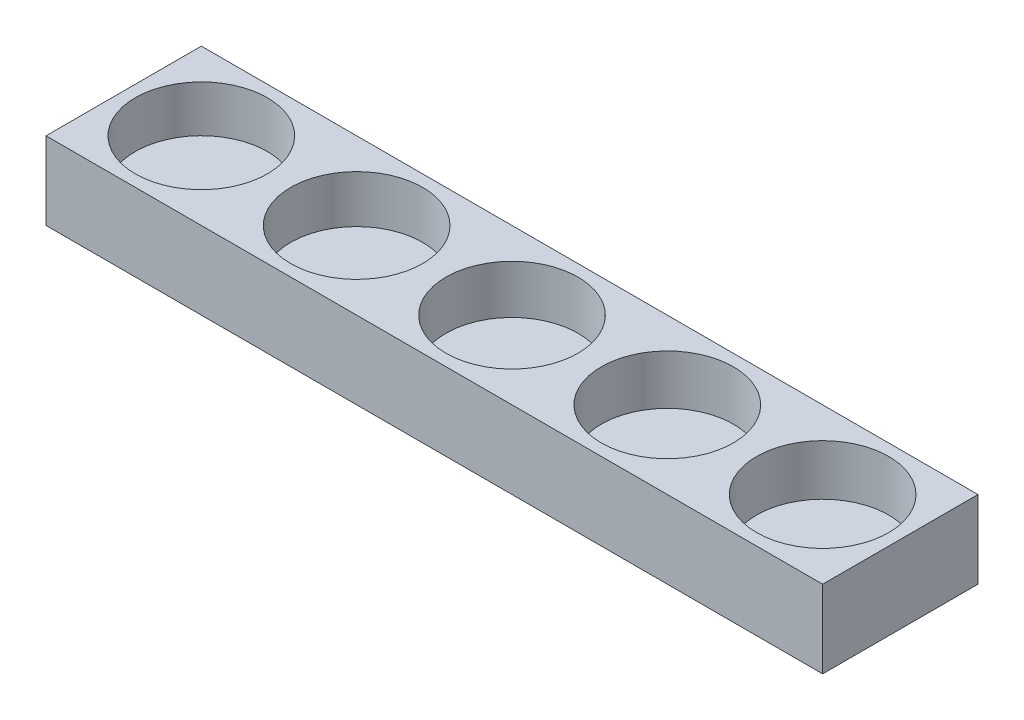
SolidWorks part; units mm, degrees
ref_plane "Front Plane" through (0, 0, 0) normal (0, 0, 1) x (1, 0, 0)
ref_plane "Top Plane" through (0, 0, 0) normal (0, 1, 0) x (1, 0, 0)
ref_plane "Right Plane" through (0, 0, 0) normal (1, 0, 0) x (0, 0, -1)
sketch "Sketch1" plane through (0, 0, 0) normal (0, 1, 0) x (1, 0, 0)
  line L0 (-75, 0) -> (75, 0) construction
  line L1 (75, -15) -> (-75, -15)
  line L2 (75, -15) -> (75, 15)
  line L3 (75, 15) -> (-75, 15)
  line L4 (-75, -15) -> (-75, 15)
  line L5 (75, -15) -> (-75, 15) construction
  line L6 (75, 15) -> (-75, -15) construction
  circle A0 centre (-60, 0) radius 5
  circle A1 centre (-30, 0) radius 5
  circle A2 centre (0, 0) radius 5
  circle A3 centre (30, 0) radius 5
  circle A4 centre (60, 0) radius 5
  point P0 (0, 0)
  dimension "D3" = 10
  dimension "D1" = 150
  dimension "D2" = 30
  dimension "D4" = 15
  dimension "D6" = 30
  dimension "D5" = 5
extrude "Boss-Extrude1" add sketch "Sketch1" along normal blind 5
sketch "Sketch2" plane through (0, 5, 0) normal (0, 1, 0) x (1, 0, 0)
  line L1 (-75, 15) -> (75, 15)
  line L2 (-75, 15) -> (-75, -15)
  line L3 (-75, -15) -> (75, -15)
  line L4 (75, 15) -> (75, -15)
extrude "Boss-Extrude2" add sketch "Sketch2" along normal blind 10
sketch "Sketch3" plane through (0, 15, 0) normal (0, 1, 0) x (1, 0, 0)
  circle A0 centre (60, 0) radius 5 construction
  circle A1 centre (30, 0) radius 5 construction
  circle A2 centre (0, 0) radius 5 construction
  circle A3 centre (-30, 0) radius 5 construction
  circle A4 centre (-60, 0) radius 5 construction
  circle A5 centre (60, 0) radius 5 construction
  circle A6 centre (30, 0) radius 5 construction
  circle A7 centre (0, 0) radius 5 construction
  circle A8 centre (-30, 0) radius 5 construction
  circle A9 centre (-60, 0) radius 5 construction
  circle A10 centre (-60, 0) radius 12.75
  circle A11 centre (-30, 0) radius 12.75
  circle A12 centre (0, 0) radius 12.75
  circle A13 centre (30, 0) radius 12.75
  circle A14 centre (60, 0) radius 12.75
  dimension "D1" = 25.5
extrude "Cut-Extrude1" cut sketch "Sketch3" against normal offset from surface (9 mm away) 1 contours A10 region at (-60, 15, 0) up to face at (-60, 5, 5)
extrude "Cut-Extrude2" cut sketch "Sketch3<3>" against normal offset from surface (9.2 mm away) 0.8 contours A11 region at (-30, 15, 0) up to face at (-30, 5, 5)
sketch "Sketch3<3>" plane through (0, 15, 0) normal (0, 1, 0) x (1, 0, 0) same geometry as "Sketch3"
extrude "Cut-Extrude3" cut sketch "Sketch3<4>" against normal offset from surface (9.4 mm away) 0.6 contours A12 region at (0, 15, 0) up to face at (0, 5, 5)
sketch "Sketch3<4>" plane through (0, 15, 0) normal (0, 1, 0) x (1, 0, 0) same geometry as "Sketch3"
extrude "Cut-Extrude4" cut sketch "Sketch3<5>" against normal offset from surface (9.6 mm away) 0.4 contours A13 region at (30, 15, 0) up to face at (30, 5, 5)
sketch "Sketch3<5>" plane through (0, 15, 0) normal (0, 1, 0) x (1, 0, 0) same geometry as "Sketch3"
extrude "Cut-Extrude5" cut sketch "Sketch3<6>" against normal offset from surface (9.8 mm away) 0.2 contours A14 region at (60, 15, 0) up to face at (60, 5, 5)
sketch "Sketch3<6>" plane through (0, 15, 0) normal (0, 1, 0) x (1, 0, 0) same geometry as "Sketch3"
